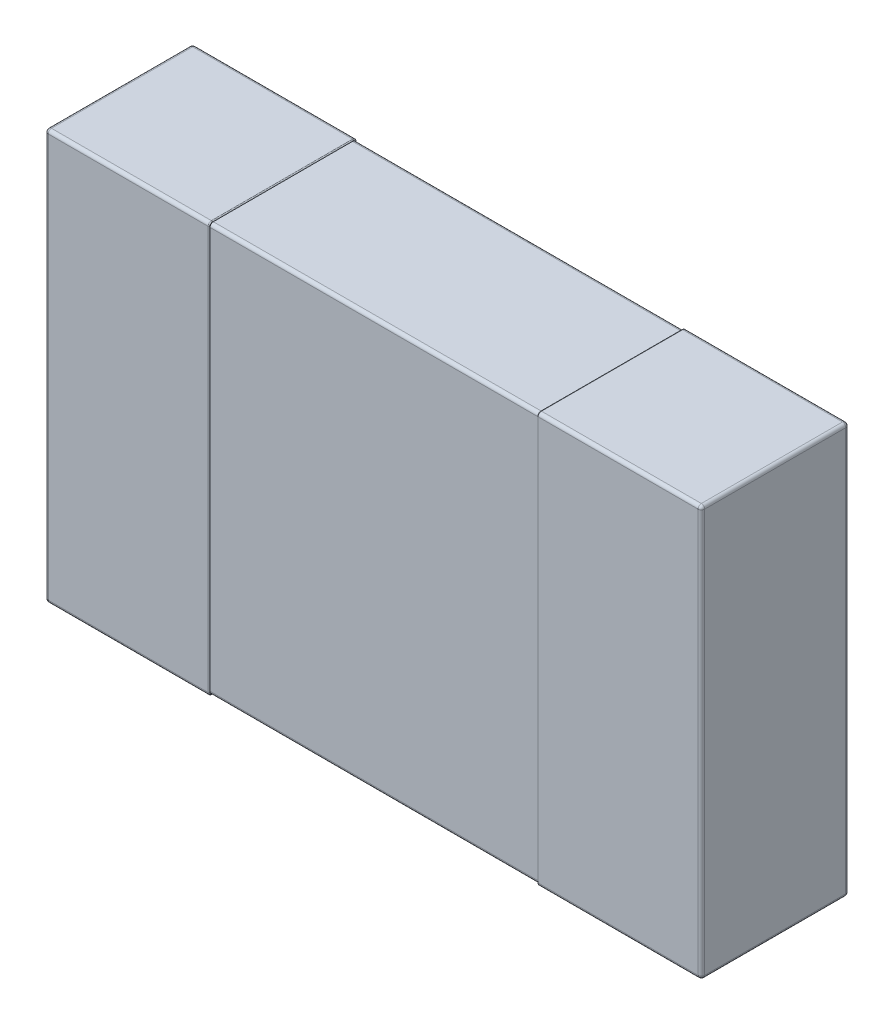
SolidWorks part; units mm, degrees
ref_plane "Top Plane" through (0, 0, 0) normal (0, 0, 1) x (1, 0, 0)
ref_plane "Front Plane" through (0, 0, 0) normal (0, 1, 0) x (1, 0, 0)
ref_plane "Side Plane" through (0, 0, 0) normal (1, 0, 0) x (0, 0, -1)
sketch "Sketch1" plane through (0, 0, 0) normal (0, 0, 1) x (1, 0, 0)
  line L1 (-1, 0.625) -> (1, 0.625)
  line L2 (-1, 0.625) -> (-1, -0.625)
  line L3 (-1, -0.625) -> (1, -0.625)
  line L4 (1, 0.625) -> (1, -0.625)
  dimension "D1" = 2
  dimension "D2" = 1
  dimension "D3" = 1.25
  dimension "D4" = 0.625
extrude "All body" add sketch "Sketch1" along normal blind 0.45
sketch "Sketch2" plane through (0, 0, 0) normal (1, 0, 0) x (0, 0, -1)
  line L14 (-0.003, 0.622) -> (-0.447, 0.622)
  line L15 (-0.003, -0.622) -> (-0.003, 0.622)
  line L16 (-0.447, -0.622) -> (-0.003, -0.622)
  line L17 (-0.447, 0.622) -> (-0.447, -0.622)
  line L18 (-0.003, 0.622) -> (-0.447, 0.622)
  line L19 (-0.003, -0.622) -> (-0.003, 0.622)
  line L20 (-0.447, -0.622) -> (-0.003, -0.622)
  line L21 (-0.447, 0.622) -> (-0.447, -0.622)
  dimension "D1" = 0.003
extrude "Cut out the body for pin" cut sketch "Sketch2" against normal blind 0.5 and the other way blind 0.5 flip side to cut
fillet "Body fillet" radius 0.01 4 edges at (0, 0.622, 0.003) (0, 0.622, 0.447) (0, -0.622, 0.003) (0, -0.622, 0.447)
fillet "Pin fillet a" radius 0.01 16 edges at (1, -0.625, 0.225) (1, 0, 0.45) (1, 0.625, 0.225) (1, 0, 0) (-1, 0.625, 0.225) (-1, 0, 0.45) (-1, -0.625, 0.225) (-1, 0, 0) (0.75, 0.625, 0.45) (0.75, -0.625, 0.45) (0.75, -0.625, 0) (0.75, 0.625, 0) (-0.75, 0.625, 0) (-0.75, -0.625, 0) (-0.75, 0.625, 0.45) (-0.75, -0.625, 0.45)
fillet "Pin fillet b" radius 0.003 16 edges at (0.5, -0.6221, 0.4471) (0.5, -0.625, 0.225) (0.5, -0.6221, 0.0029) (0.5, 0, 0) (0.5, 0.6221, 0.0029) (0.5, 0.625, 0.225) (0.5, 0.6221, 0.4471) (-0.5, -0.6221, 0.4471) (-0.5, -0.625, 0.225) (-0.5, -0.6221, 0.0029) (-0.5, 0, 0) (-0.5, 0.6221, 0.0029) (-0.5, 0.625, 0.225) (-0.5, 0.6221, 0.4471) (0.5, 0, 0.45) (-0.5, 0, 0.45)
